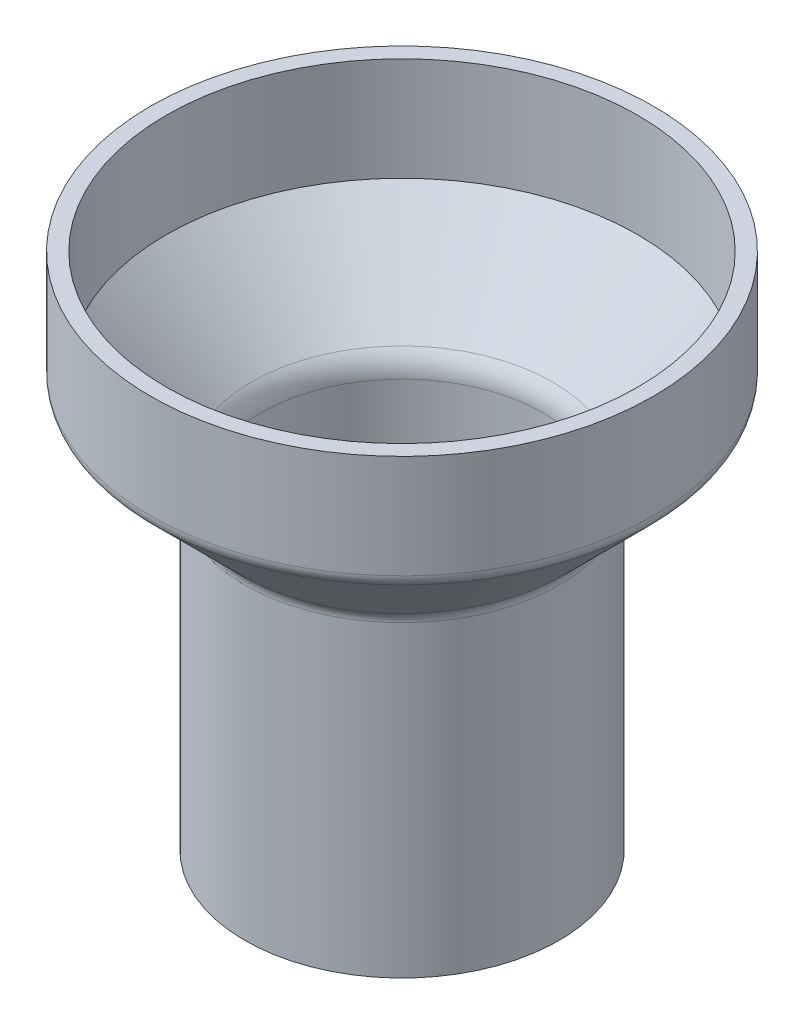
SolidWorks part; units mm, degrees
ref_plane "Спереди" through (0, 0, 0) normal (0, 0, 1) x (1, 0, 0)
ref_plane "Сверху" through (0, 0, 0) normal (0, 1, 0) x (1, 0, 0)
ref_plane "Справа" through (0, 0, 0) normal (1, 0, 0) x (0, 0, -1)
sketch "Эскиз1" plane through (0, 0, 0) normal (0, 0, 1) x (1, 0, 0)
  line L0 (0, 0) -> (-10, 0)
  line L1 (-10, 0) -> (-10, 20)
  line L2 (-10, 20) -> (-16, 26)
  line L3 (-16, 26) -> (-16, 33)
  line L4 (-16, 33) -> (0, 33)
  line L5 (0, 33) -> (0, 0)
  dimension "D1" = 33
  dimension "D2" = 45
  dimension "D3" = 20
  dimension "D4" = 10
  dimension "D5" = 16
revolve "Повернуть1" add sketch "Эскиз1" angle 360 about L5
fillet "Скругление1" radius 1 2 edges at (-16, 26, 0) (-10, 20, 0)
shell "Оболочка1" thickness 1 removed face at (-10, 0, 0) removed face at (-16, 33, 0)
